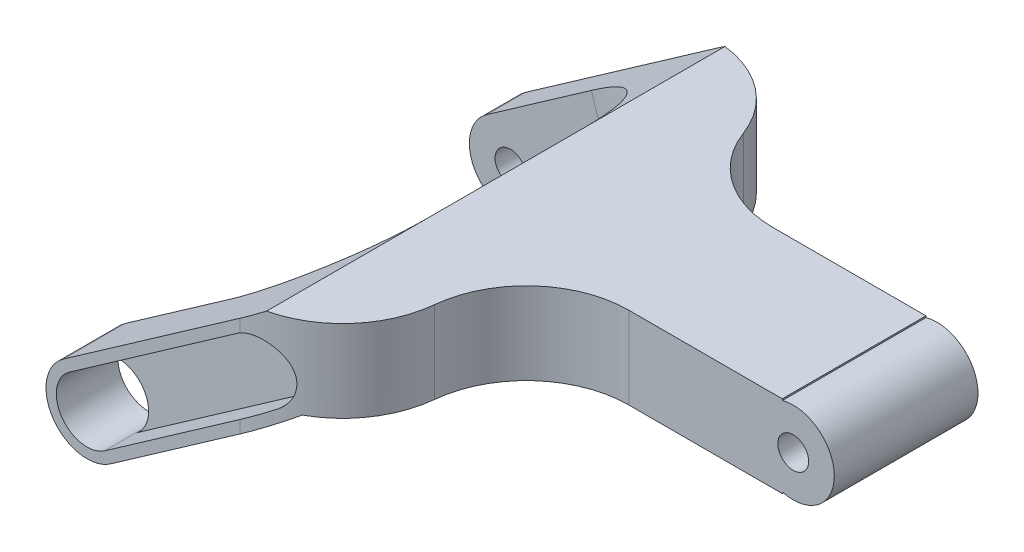
SolidWorks part; units mm, degrees
ref_plane "前视基准面" through (0, 0, 0) normal (0, 0, 1) x (1, 0, 0)
ref_plane "上视基准面" through (0, 0, 0) normal (0, 1, 0) x (1, 0, 0)
ref_plane "右视基准面" through (0, 0, 0) normal (1, 0, 0) x (0, 0, -1)
sketch "草图1" plane through (0, 0, 0) normal (0, 0, 1) x (1, 0, 0)
  line L0 (15.6052, 4.0165) -> (15.6052, 4.1614)
  line L1 (15.6052, -3.8386) -> (-14.3948, -3.8386)
  line L2 (15.6052, -3.8386) -> (15.6052, -3.6938)
  line L3 (15.6052, 4.1614) -> (-16.9172, 4.1614)
  line L7 (-14.3948, -3.8386) -> (-31.8334, -16.0492)
  line L8 (-36.422, -9.496) -> (-16.9172, 4.1614)
  line L9 (-34.1277, -1012.7726) -> (-34.1277, 48987.2274) construction
  line L10 (16.6718, -999.8386) -> (16.6718, 49000.1614) construction
  arc A0 (15.6052, -3.6938) -> (15.6052, 4.0165) centre (16.6718, 0.1614) ccw
  arc A1 (-36.422, -9.496) -> (-31.8334, -16.0492) centre (-34.1277, -12.7726) ccw
  circle A2 centre (-34.1277, -12.7726) radius 1.5
  circle A3 centre (16.6718, 0.1614) radius 1.5
  point P0 (0, 0)
  dimension "D3" = 8
  dimension "D6" = 8
  dimension "D7" = 3
  dimension "D8" = 3
  dimension "D1" = 8
  dimension "D2" = 30
  dimension "D4" = 145
  dimension "D5" = 8
  dimension "D9" = 50.7995
extrude "凸台-拉伸2" add sketch "草图1" along normal blind 50
sketch "草图14" plane through (0, -3.8386, 0) normal (0, -1, 0) x (1, 0, 0)
  line L0 (-16.9172, 25) -> (49983.0828, 25) construction
  line L1 (-16.9172, 50) -> (-16.9172, 0) construction
  line L2 (20.6718, 50) -> (20.6718, 32)
  line L3 (20.6718, 0) -> (-9.3282, 0)
  line L4 (20.6718, 0) -> (20.6718, 18)
  line L5 (20.6718, 18) -> (-9.3282, 18)
  line L6 (-9.3282, 0) -> (-9.3282, 18)
  line L7 (20.6718, 50) -> (-9.3282, 50)
  line L8 (20.6718, 32) -> (-9.3282, 32)
  line L9 (-9.3282, 50) -> (-9.3282, 32)
  point P4 (-16.9172, 25)
  dimension "D1" = 7
  dimension "D2" = 30
extrude "切除-拉伸6" cut sketch "草图14" against normal through all
sketch "草图15" plane through (0, 4.1614, 0) normal (0, 1, 0) x (1, 0, 0)
  line L0 (20.6718, -25) -> (-49979.3282, -25) construction
  line L1 (20.6718, -32) -> (20.6718, -18) construction
  line L2 (-16.9172, -50) -> (-16.9172, 0) construction
  line L3 (-39.3648, -25) -> (-16.9172, -25)
  line L4 (-39.3648, -25) -> (-39.3648, -8.75)
  line L5 (-39.3648, -8.75) -> (-16.9172, -8.75)
  line L6 (-16.9172, -25) -> (-16.9172, -8.75)
  point P4 (20.6718, -25)
  dimension "D1" = 16.25
  dimension "D2" = 22.4476
extrude "切除-拉伸7" cut sketch "草图15" against normal blind 30
sketch "草图17" plane through (0, 4.1614, 0) normal (0, 1, 0) x (1, 0, 0)
  line L1 (-16.9172, -25) -> (-42.2771, -25)
  line L2 (-16.9172, -25) -> (-16.9172, -44)
  line L3 (-16.9172, -44) -> (-42.2771, -44)
  line L4 (-42.2771, -25) -> (-42.2771, -44)
  dimension "D1" = 19
  dimension "D2" = 25.3598
extrude "切除-拉伸9" cut sketch "草图17" against normal blind 30
fillet "圆角8" radius 10 1 edges at (-16.9172, -5.6048, 26.375)
sketch "草图19" plane through (-7.5208, 10.7408, 0) normal (-0.5736, 0.8192, 0) x (0.8192, 0.5736, 0)
  line L1 (-39.2819, 0) -> (-5.2543, 0)
  line L2 (-39.2819, 0) -> (-39.2819, -5)
  line L3 (-39.2819, -5) -> (-5.2543, -5)
  line L4 (-5.2543, 0) -> (-5.2543, -5)
  line L5 (-5.2543, -18) -> (-5.2543, 0) construction
  dimension "D1" = 5
  dimension "D2" = 34.0275
extrude "切除-拉伸11" cut sketch "草图19" against normal through all
fillet "圆角9" radius 10 2 edges at (-9.3282, 0.1614, 32) (-9.3282, 0.1614, 18)
fillet "圆角11" radius 10 4 edges at (-16.9172, 3.4812, 44) (-16.9172, 3.4812, 8.75) (-16.2654, -0.7503, 44) (-16.2654, -0.7503, 8.75)
fillet "圆角12" radius 10 2 edges at (-9.3282, 0.1614, 50) (-9.3282, 0.1614, 5)
sketch "草图20" plane through (0, 0, 50) normal (0, 0, 1) x (1, 0, 0)
  line L0 (-35.8484, -10.3152) -> (-19.4654, 1.1564)
  line L1 (-32.407, -15.2301) -> (-16.0239, -3.7586)
  line L2 (-852.8272, -586.0322) -> (-36.5852, -14.4934) construction
  line L3 (-19.2279, 2.5434) -> (-36.422, -9.496) construction
  line L4 (-15.2872, 0.4196) -> (40923.9271, 28666.3661) construction
  line L5 (-32.4894, -11.6255) -> (-27.1418, -7.8811) construction
  arc A0 (-35.8484, -10.3152) -> (-32.407, -15.2301) centre (-34.1277, -12.7726) ccw
  arc A1 (-16.0239, -3.7586) -> (-19.4654, 1.1564) centre (-17.7447, -1.3011) ccw
  dimension "D1" = 3
  dimension "D2" = 20
extrude "切除-拉伸12" cut sketch "草图20" against normal blind 3
sketch "草图21" plane through (0, 0, 44) normal (0, 0, -1) x (-1, 0, 0)
  circle A0 centre (34.1277, -12.7726) radius 3
  dimension "D1" = 6
extrude "切除-拉伸13" cut sketch "草图21" against normal blind 5
